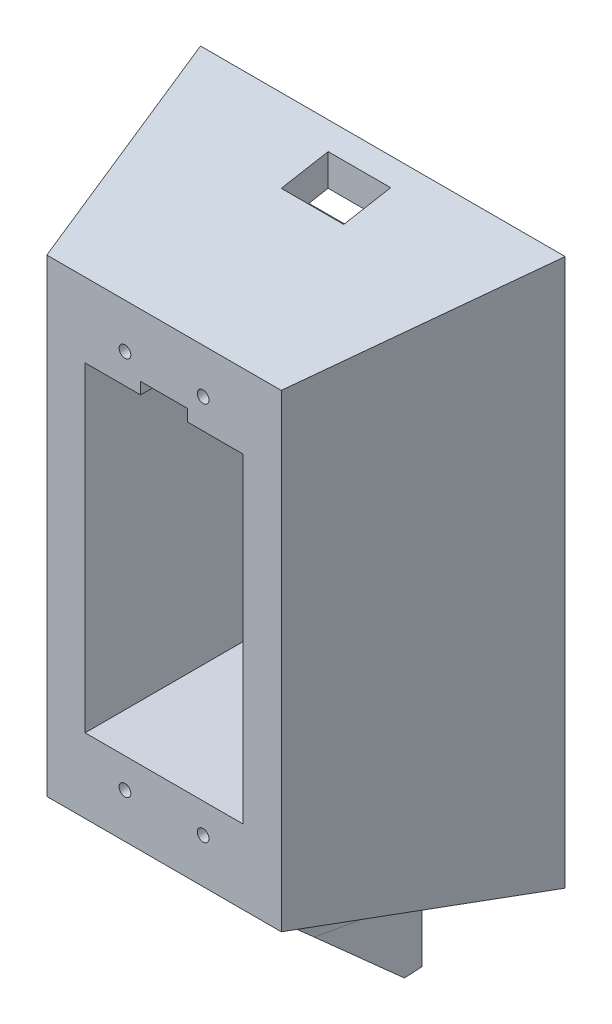
SolidWorks part; units mm, degrees
ref_plane "Plano frontal" through (0, 0, 0) normal (0, 0, 1) x (1, 0, 0)
ref_plane "Plano superior" through (0, 0, 0) normal (0, 1, 0) x (1, 0, 0)
ref_plane "Plano direito" through (0, 0, 0) normal (1, 0, 0) x (0, 0, -1)
sketch "Esboço1" plane through (0, 0, 0) normal (0, 0, 1) x (1, 0, 0)
  line L1 (-15, -30) -> (15, -30)
  line L2 (-15, -30) -> (-15, 30)
  line L3 (-15, 30) -> (15, 30)
  line L4 (15, -30) -> (15, 30)
  line L5 (-15, -30) -> (15, 30) construction
  line L6 (-15, 30) -> (15, -30) construction
  point P0 (0, 0)
  dimension "D1" = 60
ref_plane "Plano1" through (0, 0, -28) normal (0, 0, 1) x (1, 0, 0)
sketch "Esboço2" plane through (0, 0, -28) normal (0, 0, 1) x (1, 0, 0)
  line L1 (-23.3333, -35) -> (23.3333, -35)
  line L2 (-23.3333, -35) -> (-23.3333, 35)
  line L3 (-23.3333, 35) -> (23.3333, 35)
  line L4 (23.3333, -35) -> (23.3333, 35)
  line L5 (-23.3333, -35) -> (23.3333, 35) construction
  line L6 (-23.3333, 35) -> (23.3333, -35) construction
  dimension "D1" = 70
loft "Loft1" add profiles "Esboço1", "Esboço2" connector at (-15, -30, 0) connector at (-23.3333, -35, -28)
sketch "Esboço3" plane through (0, 0, 0) normal (0, 0, 1) x (1, 0, 0)
  line L1 (-10.1, -20.5) -> (10.1, -20.5)
  line L2 (-10.1, -20.5) -> (-10.1, 20.5)
  line L3 (-10.1, 20.5) -> (10.1, 20.5)
  line L4 (10.1, -20.5) -> (10.1, 20.5)
  line L5 (-10.1, -20.5) -> (10.1, 20.5) construction
  line L6 (-10.1, 20.5) -> (10.1, -20.5) construction
  point P0 (0, 0)
  dimension "D1" = 41
  dimension "D2" = 20.2
extrude "Corte-extrusão1" cut sketch "Esboço3" against normal through all
shell "Casca1" thickness 4 removed face at (0, 0, -28)
sketch "Esboço5" plane through (0, 0, -28) normal (0, 0, 1) x (1, 0, 0)
  line L0 (0, 0) -> (0, 6.0662) construction
  line L1 (0, 0) -> (5.9294, 0) construction
  line L31 (10.1, 20.5) -> (10.1, 30.9367)
  line L32 (19.1599, 30.9367) -> (-19.1599, 30.9367) construction
  line L33 (10.1, 30.9367) -> (19.1599, 30.9367)
  line L34 (19.1599, 30.9367) -> (19.1599, 20.5)
  line L35 (19.1599, -30.9367) -> (19.1599, 30.9367) construction
  line L36 (19.1599, 20.5) -> (10.1, 20.5)
  line L37 (19.1599, -20.5) -> (10.1, -20.5)
  line L38 (19.1599, -30.9367) -> (19.1599, -20.5)
  line L39 (10.1, -30.9367) -> (19.1599, -30.9367)
  line L40 (10.1, -20.5) -> (10.1, -30.9367)
  line L41 (-10.1, -20.5) -> (-10.1, -30.9367)
  line L42 (-10.1, -30.9367) -> (-19.1599, -30.9367)
  line L43 (-19.1599, -30.9367) -> (-19.1599, -20.5)
  line L44 (-19.1599, -20.5) -> (-10.1, -20.5)
  line L45 (-19.1599, 20.5) -> (-10.1, 20.5)
  line L46 (-19.1599, 30.9367) -> (-19.1599, 20.5)
  line L47 (-10.1, 30.9367) -> (-19.1599, 30.9367)
  line L48 (-10.1, 20.5) -> (-10.1, 30.9367)
extrude "Ressalto-extrusão3" add sketch "Esboço5" along normal up to next
sketch "Esboço6" plane through (0, 0, -28) normal (0, 0, -1) x (-1, 0, 0)
  line L2 (0, 0) -> (0, 4.4519) construction
  line L3 (0, 0) -> (-5.2651, 0) construction
  circle A0 centre (-15, 25) radius 0.5
  circle A1 centre (15, 25) radius 0.5
  circle A2 centre (15, -25) radius 0.5
  circle A3 centre (-15, -25) radius 0.5
  dimension "D1" = 1
  dimension "D2" = 30
  dimension "D3" = 50
extrude "Corte-extrusão2" cut sketch "Esboço6" against normal blind 5
sketch "Esboço7" plane through (0, 0, 0) normal (0, 0, 1) x (1, 0, 0)
  line L0 (10.1, 20.5) -> (-10.1, 20.5) construction
  line L1 (-5, 24.3) -> (5, 24.3) construction
  line L2 (0, 0) -> (-2.5167, 0) construction
  line L3 (-10.1, -20.5) -> (10.1, -20.5) construction
  circle A0 centre (-5, 24.3) radius 0.75
  circle A1 centre (5, 24.3) radius 0.75
  circle A2 centre (-5, -24.3) radius 0.75
  circle A3 centre (5, -24.3) radius 0.75
  point P6 (0, 24.3)
  point P7 (0, 20.5)
  point P15 (0, 0)
  dimension "D1" = 10
  dimension "D3" = 1.5
  dimension "D4" = 1.5
  dimension "D2" = 3.8
  dimension "D5" = 3.8
extrude "Corte-extrusão3" cut sketch "Esboço7" against normal blind 3
sketch "Esboço8" plane through (0, 0, 0) normal (1, 0, 0) x (0, 0, -1)
  line L0 (28, -35) -> (28, -55)
  line L2 (0, -30) -> (28, -35)
  line L7 (0, -30) -> (28, -55)
  dimension "D1" = 20
extrude "Ressalto-extrusão4" add sketch "Esboço8" along normal mid plane 10
fillet "Filete2" radius 10 2 edges
chamfer "Chanfro3" distance 3 angle 45 1 edges at (0, -55, -28) first distance on face at (-0.625, -37.8867, -8.833)
sketch "Esboço9" plane through (0, 0, -28) normal (0, 0, -1) x (-1, 0, 0)
  line L0 (5, -53.002) -> (-5, -53.002) construction
  circle A0 centre (0, -45.002) radius 0.5
  dimension "D1" = 8
  dimension "D3" = 1
  dimension "D2" = 5
extrude "Corte-extrusão4" cut sketch "Esboço9" against normal blind 3
sketch "Esboço11" plane through (0, -20.5, 0.8002) normal (0, 1, 0) x (1, 0, 0)
  line L6 (-4, 25.8002) -> (4, 25.8002)
  line L8 (-4, 25.8002) -> (-4, 19.8002)
  line L9 (-4, 19.8002) -> (4, 19.8002)
  line L10 (4, 25.8002) -> (4, 19.8002)
  line L11 (-4, 25.8002) -> (4, 19.8002) construction
  line L12 (-4, 19.8002) -> (4, 25.8002) construction
  point P0 (0, 22.8002)
  dimension "D1" = 8
  dimension "D2" = 3
  dimension "D4" = 6
extrude "Corte-extrusão7" cut sketch "Esboço11" along normal through all
sketch "Esboço12" plane through (0, 0, 0) normal (0, 0, 1) x (1, 0, 0)
  line L0 (10.1, 20.5) -> (-10.1, 20.5) construction
  line L1 (-3, 19) -> (3, 19)
  line L2 (-3, 19) -> (-3, 22)
  line L3 (-3, 22) -> (3, 22)
  line L4 (3, 19) -> (3, 22)
  line L5 (-3, 19) -> (3, 22) construction
  line L6 (-3, 22) -> (3, 19) construction
  point P0 (0, 20.5)
  dimension "D1" = 6
  dimension "D2" = 3
extrude "Corte-extrusão6" cut sketch "Esboço12" against normal blind 22
